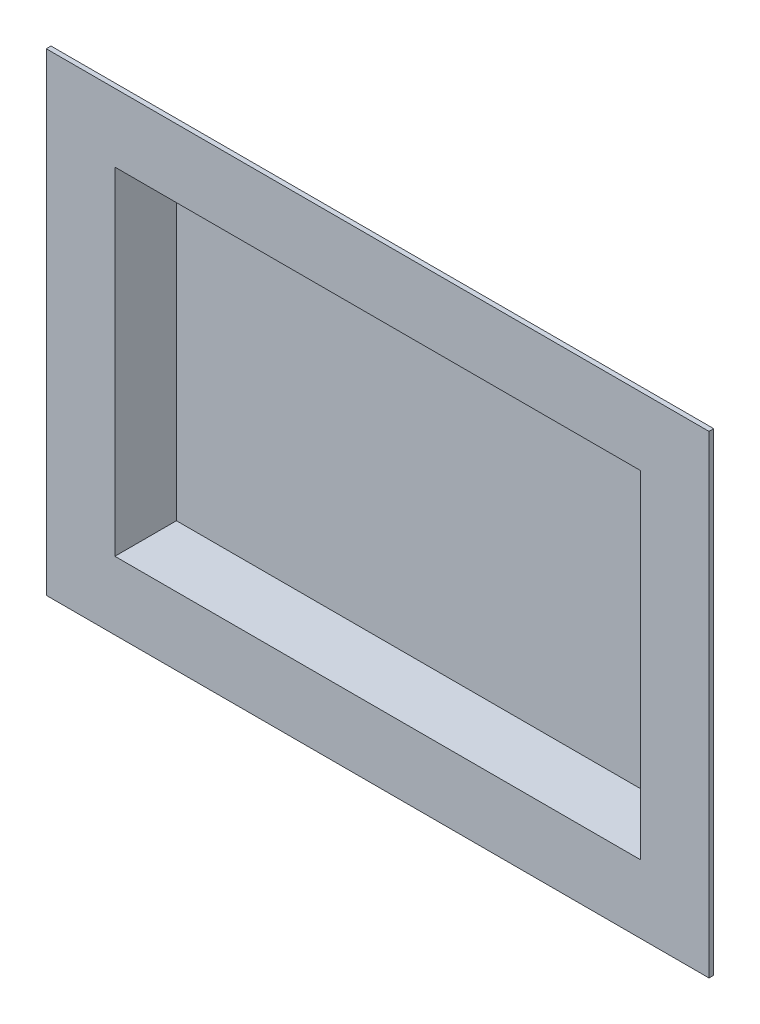
SolidWorks part; units mm, degrees
material "6063-O"
ref_plane "Front Plane" through (0, 0, 0) normal (0, 0, 1) x (1, 0, 0)
ref_plane "Top Plane" through (0, 0, 0) normal (0, 1, 0) x (1, 0, 0)
ref_plane "Right Plane" through (0, 0, 0) normal (1, 0, 0) x (0, 0, -1)
sketch "Sketch1" plane through (0, 0, 0) normal (0, 0, 1) x (1, 0, 0)
  line L1 (-71.755, -46.482) -> (71.755, -46.482)
  line L2 (-71.755, -46.482) -> (-71.755, 46.482)
  line L3 (-71.755, 46.482) -> (71.755, 46.482)
  line L4 (71.755, -46.482) -> (71.755, 46.482)
  line L5 (-71.755, -46.482) -> (71.755, 46.482) construction
  line L6 (-71.755, 46.482) -> (71.755, -46.482) construction
  point P0 (0, 0)
  dimension "D1" = 143.51
  dimension "D2" = 92.964
extrude "Boss-Extrude1" add sketch "Sketch1" against normal blind 16.51
sketch "Sketch2" plane through (0, 0, 0) normal (0, 0, 1) x (1, 0, 0)
  line L1 (-88.9, -63.5) -> (88.9, -63.5)
  line L2 (-88.9, -63.5) -> (-88.9, 63.5)
  line L3 (-88.9, 63.5) -> (88.9, 63.5)
  line L4 (88.9, -63.5) -> (88.9, 63.5)
  line L5 (-88.9, -63.5) -> (88.9, 63.5) construction
  line L6 (-88.9, 63.5) -> (88.9, -63.5) construction
  point P0 (0, 0)
  dimension "D1" = 177.8
  dimension "D2" = 127
extrude "Boss-Extrude2" add sketch "Sketch2" along normal blind 1.27
shell "Shell1" thickness 1.27 removed face at (0, 0, 1.27)
